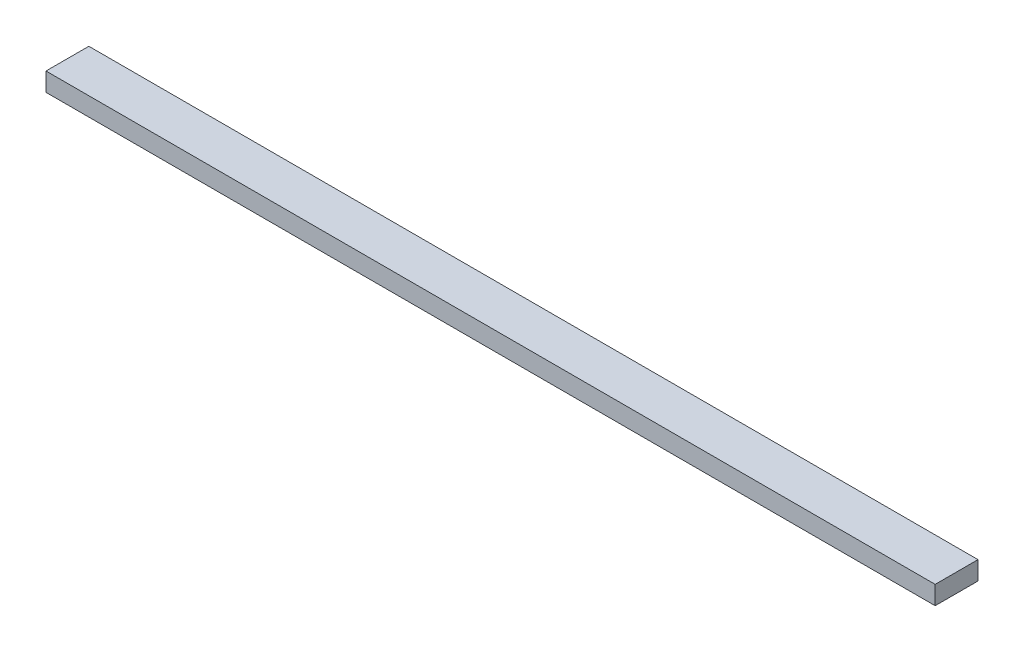
SolidWorks part; units mm, degrees
material "Pine"
ref_plane "Front Plane" through (0, 0, 0) normal (0, 0, 1) x (1, 0, 0)
ref_plane "Top Plane" through (0, 0, 0) normal (0, 1, 0) x (1, 0, 0)
ref_plane "Right Plane" through (0, 0, 0) normal (1, 0, 0) x (0, 0, -1)
sketch "Sketch1" plane through (0, 0, 0) normal (1, 0, 0) x (0, 0, -1)
  line L1 (44.0531, -19.05) -> (-44.0531, -19.05)
  line L2 (44.0531, -19.05) -> (44.0531, 19.05)
  line L3 (44.0531, 19.05) -> (-44.0531, 19.05)
  line L4 (-44.0531, -19.05) -> (-44.0531, 19.05)
  line L5 (44.0531, -19.05) -> (-44.0531, 19.05) construction
  line L6 (44.0531, 19.05) -> (-44.0531, -19.05) construction
  point P0 (0, 0)
  dimension "D1" = 88.1063
  dimension "D2" = 38.1
extrude "Boss-Extrude1" add sketch "Sketch1" along normal blind 1828.8
